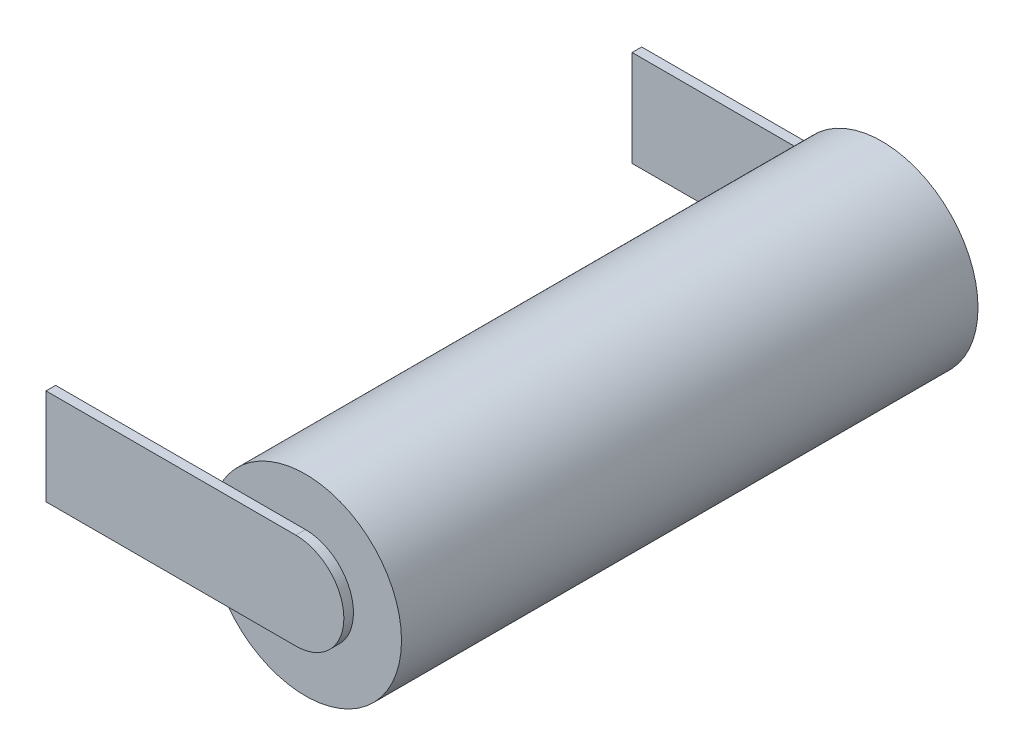
SolidWorks part; units mm, degrees
material "Wrought Stainless Steel"
ref_plane "Front Plane" through (0, 0, 0) normal (0, 0, 1) x (1, 0, 0)
ref_plane "Top Plane" through (0, 0, 0) normal (0, 1, 0) x (1, 0, 0)
ref_plane "Right Plane" through (0, 0, 0) normal (1, 0, 0) x (0, 0, -1)
sketch "Sketch1" plane through (0, 0, 0) normal (1, 0, 0) x (0, 0, -1)
  line L0 (-15, 0) -> (15, 0)
  line L1 (-15, 0) -> (-15, 5)
  line L2 (-15, 5) -> (15, 5)
  line L3 (15, 5) -> (15, 0)
  point P4 (0, 0)
  dimension "D1" = 5
  dimension "D2" = 30
revolve "Revolve1" add sketch "Sketch1" angle 360 about L0
sketch "Sketch2" plane through (0, 0, 0) normal (0, 0, 1) x (1, 0, 0)
  line L1 (-13, -2.5) -> (0, -2.5)
  line L2 (-13, -2.5) -> (-13, 2.5)
  line L3 (-13, 2.5) -> (0, 2.5)
  line L4 (0, -2.5) -> (0, 2.5) construction
  line L5 (-13, -2.5) -> (0, 2.5) construction
  line L6 (-13, 2.5) -> (0, -2.5) construction
  arc A0 (0, 2.5) -> (0, -2.5) centre (0, 0) cw
  point P0 (-6.5, 0)
  dimension "D1" = 5
  dimension "D2" = 13
extrude "Boss-Extrude1" add sketch "Sketch2" along normal blind 0.5 from surface starting at face at (5, 0, 15)
extrude "Boss-Extrude2" add sketch "Sketch2<2>" against normal blind 0.5 from surface starting at face at (5, 0, -15)
sketch "Sketch2<2>" plane through (0, 0, 0) normal (0, 0, 1) x (1, 0, 0) same geometry as "Sketch2"
